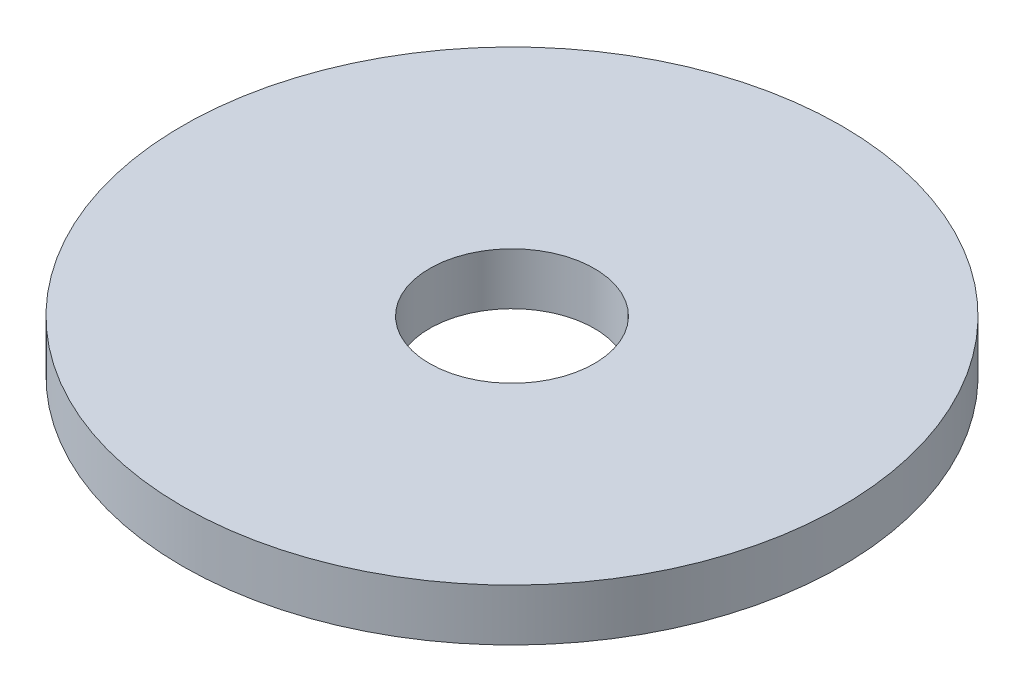
SolidWorks part; units mm, degrees
ref_plane "Front Plane" through (0, 0, 0) normal (0, 0, 1) x (1, 0, 0)
ref_plane "Top Plane" through (0, 0, 0) normal (0, 1, 0) x (1, 0, 0)
ref_plane "Right Plane" through (0, 0, 0) normal (1, 0, 0) x (0, 0, -1)
ref_axis "Axis1" through (0, 5.715, 0) along (0, -1, 0)
sketch "Sketch1" plane through (0, 0, 0) normal (0, 0, 1) x (1, 0, 0)
  line L0 (0, 299.5448) -> (0, -168.0779) construction
  line L1 (-2.3812, 0) -> (-9.525, 0)
  line L2 (-9.525, 0) -> (-9.525, -1.5)
  line L3 (-9.525, -1.5) -> (-2.3812, -1.5)
  line L4 (-2.3812, -1.5) -> (-2.3812, 0)
  dimension "D1" = 19.05
  dimension "D2" = 1.5
  dimension "D6" = 4.7625
revolve "Revolve1" add sketch "Sketch1" angle 360 about L0
